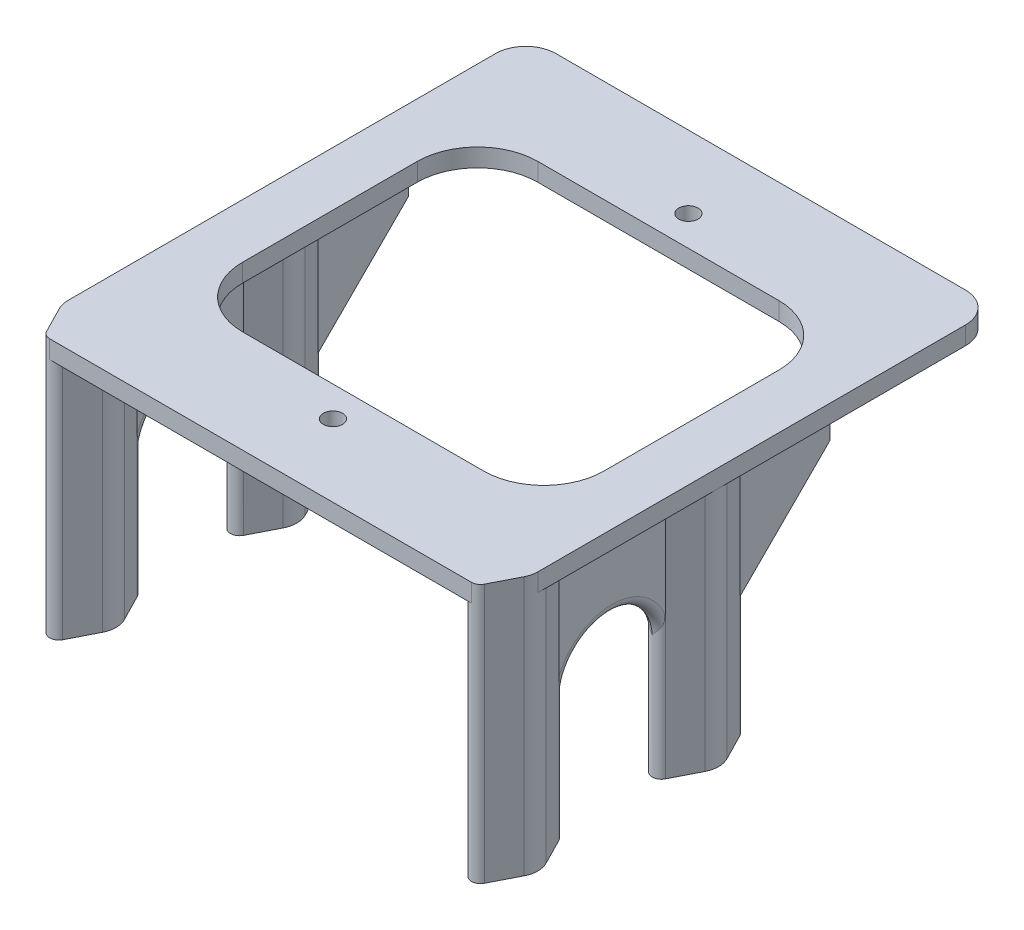
SolidWorks part; units mm, degrees
ref_plane "Front Plane" through (0, 0, 0) normal (0, 0, 1) x (1, 0, 0)
ref_plane "Top Plane" through (0, 0, 0) normal (0, 1, 0) x (1, 0, 0)
ref_plane "Right Plane" through (0, 0, 0) normal (1, 0, 0) x (0, 0, -1)
sketch "Sketch1" plane through (0, 0, 0) normal (0, 1, 0) x (1, 0, 0)
  line L0 (-1.3361, 6.1818) -> (-3.5629, 1.8182)
  line L1 (-3.5629, -1.8182) -> (-1.3361, -6.1818)
  line L2 (1.3361, -6.1818) -> (3.5629, -1.8182)
  line L3 (1.3361, 6.1818) -> (3.5629, 1.8182)
  line L4 (68.6639, 6.1818) -> (66.4371, 1.8182)
  line L5 (71.3361, 6.1818) -> (73.5629, 1.8182)
  line L6 (71.3361, -6.1818) -> (73.5629, -1.8182)
  line L7 (66.4371, -1.8182) -> (68.6639, -6.1818)
  line L8 (68.6639, -23.8182) -> (66.4371, -28.1818)
  line L9 (71.3361, -23.8182) -> (73.5629, -28.1818)
  line L10 (71.3361, -36.1818) -> (73.5629, -31.8182)
  line L11 (66.4371, -31.8182) -> (68.6639, -36.1818)
  line L12 (-1.3361, -23.8182) -> (-3.5629, -28.1818)
  line L13 (1.3361, -23.8182) -> (3.5629, -28.1818)
  line L14 (1.3361, -36.1818) -> (3.5629, -31.8182)
  line L15 (-3.5629, -31.8182) -> (-1.3361, -36.1818)
  circle A0 centre (0, 0) radius 1.6
  circle A1 centre (70, 0) radius 1.6
  circle A2 centre (0, -30) radius 1.6
  circle A3 centre (70, -30) radius 1.6
  arc A4 (-3.5629, 1.8182) -> (-3.5629, -1.8182) centre (0, 0) ccw
  arc A5 (1.3361, 6.1818) -> (-1.3361, 6.1818) centre (0, 5.5) ccw
  arc A6 (-1.3361, -6.1818) -> (1.3361, -6.1818) centre (0, -5.5) ccw
  arc A7 (3.5629, -1.8182) -> (3.5629, 1.8182) centre (0, 0) ccw
  arc A8 (71.3361, 6.1818) -> (68.6639, 6.1818) centre (70, 5.5) ccw
  arc A9 (73.5629, -1.8182) -> (73.5629, 1.8182) centre (70, 0) ccw
  arc A10 (68.6639, -6.1818) -> (71.3361, -6.1818) centre (70, -5.5) ccw
  arc A11 (66.4371, 1.8182) -> (66.4371, -1.8182) centre (70, 0) ccw
  arc A12 (71.3361, -23.8182) -> (68.6639, -23.8182) centre (70, -24.5) ccw
  arc A13 (73.5629, -31.8182) -> (73.5629, -28.1818) centre (70, -30) ccw
  arc A14 (68.6639, -36.1818) -> (71.3361, -36.1818) centre (70, -35.5) ccw
  arc A15 (66.4371, -28.1818) -> (66.4371, -31.8182) centre (70, -30) ccw
  arc A16 (1.3361, -23.8182) -> (-1.3361, -23.8182) centre (0, -24.5) ccw
  arc A17 (3.5629, -31.8182) -> (3.5629, -28.1818) centre (0, -30) ccw
  arc A18 (-1.3361, -36.1818) -> (1.3361, -36.1818) centre (0, -35.5) ccw
  arc A19 (-3.5629, -28.1818) -> (-3.5629, -31.8182) centre (0, -30) ccw
  dimension "D2" = 3.2
  dimension "D4" = 3
  dimension "D5" = 8
  dimension "D1" = 30
  dimension "D3" = 70
  dimension "D6" = 2
  dimension "D7" = 2
extrude "Boss-Extrude1" add sketch "Sketch1" along normal blind 40
sketch "Sketch2" plane through (0, 40, 0) normal (0, 1, 0) x (1, 0, 0)
  line L1 (1, 46) -> (69, 46)
  line L2 (-4, 41) -> (-4, -30)
  line L3 (0, -37) -> (70, -37)
  line L4 (74, 41) -> (74, -30)
  line L7 (71.3361, -36.1818) -> (73.5629, -31.8182)
  line L8 (-3.5629, -31.8182) -> (-1.3361, -36.1818)
  line L9 (-3.5629, -31.8182) -> (-1.3361, -36.1818)
  line L10 (71.3361, -36.1818) -> (73.5629, -31.8182)
  line L11 (15, 29) -> (55, 29)
  line L12 (5, 19) -> (5, -10)
  line L13 (15, -20) -> (55, -20)
  line L14 (65, 19) -> (65, -10)
  circle A0 centre (35, -25) radius 1.6
  circle A1 centre (35, 34) radius 1.6
  circle A2 centre (70, 0) radius 1.6 construction
  arc A3 (73.5629, -31.8182) -> (73.5629, -28.1818) centre (70, -30) ccw construction
  arc A4 (-3.5629, -28.1818) -> (-3.5629, -31.8182) centre (0, -30) ccw construction
  arc A5 (-1.3361, -36.1818) -> (1.3361, -36.1818) centre (0, -35.5) ccw construction
  circle A6 centre (0, 0) radius 1.6 construction
  arc A7 (55, -20) -> (65, -10) centre (55, -10) ccw
  arc A8 (5, -10) -> (15, -20) centre (15, -10) ccw
  arc A9 (55, 29) -> (65, 19) centre (55, 19) cw
  arc A10 (15, 29) -> (5, 19) centre (15, 19) ccw
  arc A11 (73.5629, -31.8182) -> (73.5629, -28.1818) centre (70, -30) ccw
  arc A12 (-1.3361, -36.1818) -> (1.3361, -36.1818) centre (0, -35.5) ccw
  arc A13 (-3.5629, -28.1818) -> (-3.5629, -31.8182) centre (0, -30) ccw
  arc A14 (-1.3361, -36.1818) -> (0, -37) centre (0, -35.5) ccw
  arc A15 (-4, -30) -> (-3.5629, -31.8182) centre (0, -30) ccw
  arc A16 (68.6639, -36.1818) -> (71.3361, -36.1818) centre (70, -35.5) ccw
  arc A17 (73.5629, -31.8182) -> (74, -30) centre (70, -30) ccw
  arc A18 (70, -37) -> (71.3361, -36.1818) centre (70, -35.5) ccw
  arc A19 (69, 46) -> (74, 41) centre (69, 41) cw
  arc A20 (1, 46) -> (-4, 41) centre (1, 41) ccw
  point P8 (35, 46)
  dimension "D1" = 3.2
  dimension "D11" = 10
  dimension "D12" = 5
  dimension "D2" = 59
  dimension "D5" = 12
  dimension "D6" = 12
  dimension "D7" = 5
  dimension "D8" = 5
  dimension "D9" = 5
  dimension "D10" = 5
  dimension "D3" = 0
  dimension "D4" = 0
extrude "Boss-Extrude2" add sketch "Sketch2" along normal blind 3
sketch "Sketch4" plane through (0, 40, 0) normal (0, -1, 0) x (1, 0, 0)
  line L1 (-1.3361, -6.1818) -> (1.3361, -6.1818)
  line L2 (-1.3361, -6.1818) -> (-1.3361, -21.1818)
  line L3 (-1.3361, -21.1818) -> (1.3361, -21.1818)
  line L4 (1.3361, -6.1818) -> (1.3361, -21.1818)
  line L5 (-1.3361, 23.8182) -> (1.3361, 23.8182)
  line L6 (-1.3361, 23.8182) -> (-1.3361, 6.1818)
  line L7 (-1.3361, 6.1818) -> (1.3361, 6.1818)
  line L8 (1.3361, 23.8182) -> (1.3361, 6.1818)
  dimension "D1" = 15
extrude "Boss-Extrude3" add sketch "Sketch4" along normal blind 20
ref_plane "Plane1" through (65, 43, -19) normal (0, 0, -1) x (-1, 0, 0)
sketch "Sketch6" plane through (-1.3361, 0, 0) normal (-1, 0, 0) x (0, 0, 1)
  line L0 (23.8182, 20) -> (6.1818, 20) construction
  line L1 (23, 20) -> (23, 0) construction
  circle A0 centre (15, 20) radius 8
extrude "Cut-Extrude2" cut sketch "Sketch6" against normal through all contours A0
fillet "Fillet1" radius 1.5 2 edges at (1.3361, 28, 15) (-1.3361, 28, 15)
chamfer "Chamfer1" distance 15 angle 45 1 edges at (0, 20, -21.1818)
ref_plane "Plane2" through (35, 0, 0) normal (-1, 0, 0) x (0, 0, 1)
mirror "Mirror1" about plane through (35, 0, 0) normal (-1, 0, 0) of "Chamfer1", "Cut-Extrude2", "Boss-Extrude3", "Fillet1"
